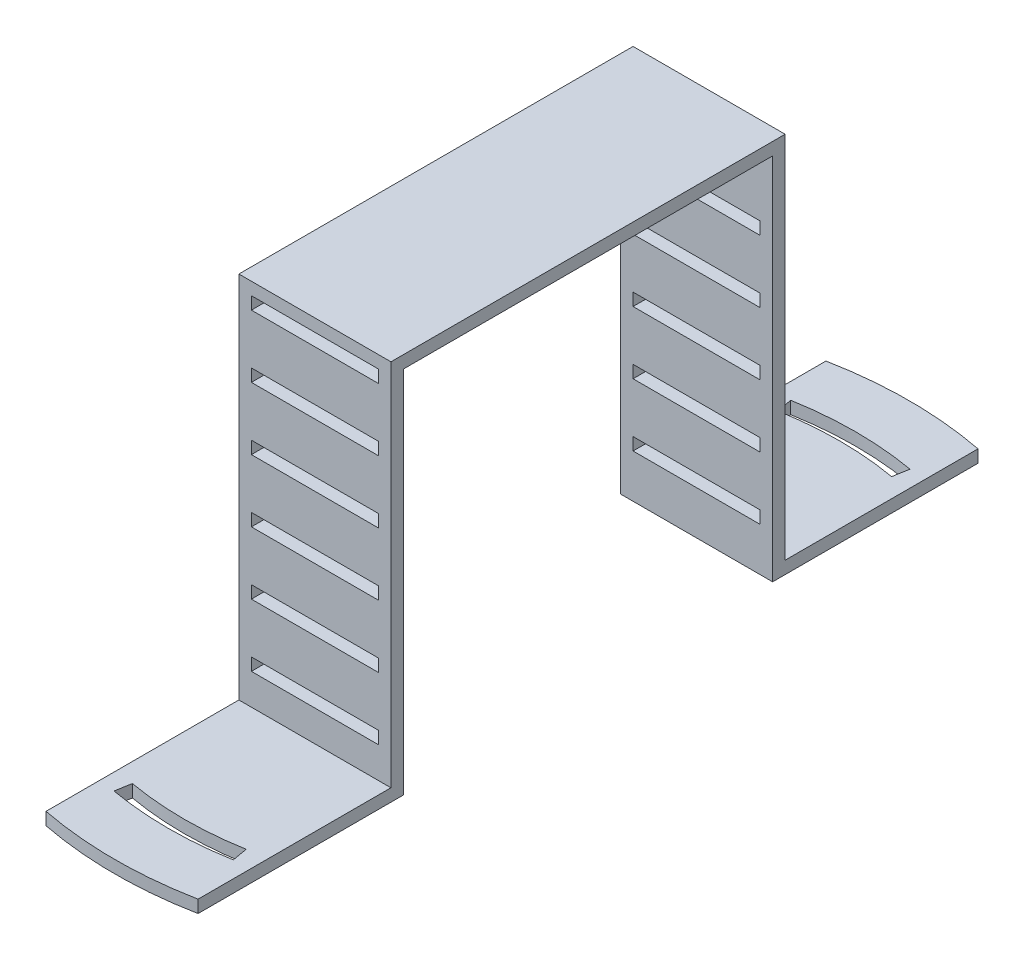
SolidWorks part; units mm, degrees
ref_plane "Front Plane" through (0, 0, 0) normal (0, 0, 1) x (1, 0, 0)
ref_plane "Top Plane" through (0, 0, 0) normal (0, 1, 0) x (1, 0, 0)
ref_plane "Right Plane" through (0, 0, 0) normal (1, 0, 0) x (0, 0, -1)
sketch "Sketch1" plane through (0, 0, 0) normal (0, 1, 0) x (1, 0, 0)
  line L0 (0, 0) -> (0, -79.375)
  line L1 (7.1438, -66.675) -> (-7.1437, -66.675)
  line L2 (50.8, 22.225) -> (76.2, 22.225)
  line L3 (-63.5, -47.625) -> (-50.8, -47.625)
  line L4 (-50.8, -47.625) -> (-50.8, 22.225)
  line L5 (63.5, -47.625) -> (50.8, -47.625)
  line L6 (50.8, -47.625) -> (50.8, 22.225)
  line L7 (-50.8, 22.225) -> (-76.2, 22.225)
  line L8 (0, 0) -> (-27.2811, 0)
  circle A0 centre (0, 0) radius 79.375
  circle A1 centre (-7.1437, -66.675) radius 1.5875
  circle A2 centre (7.1438, -66.675) radius 1.5875
  circle A3 centre (7.1438, 66.675) radius 1.5875
  circle A4 centre (-7.1437, 66.675) radius 1.5875
  point P7 (0, -66.675)
  dimension "D1" = 7.1437
  dimension "D3" = 50.8
  dimension "D6" = 3.175
  dimension "D2" = 12.7
  dimension "D4" = 69.85
  dimension "D5" = 47.625
extrude "Boss-Extrude5" add sketch "Sketch1" along normal blind 1.5875 contours A2 A0 L5 L6 L2 L7 L4 L3 A1 A3 region at (0, 0, -2.0947)
fillet "Fillet2" radius 2.54 1 edges at (-63.5, 0.7937, 47.625)
fillet "Fillet3" radius 2.54 1 edges at (63.5, 0.7937, 47.625)
fillet "Fillet4" radius 5.08 2 edges at (-76.2, 0.7937, -22.225) (76.2, 0.7937, -22.225)
sketch "Sketch2" plane through (0, 1.5875, 0) normal (0, 1, 0) x (1, 0, 0)
  line L0 (0, 0) -> (0, 79.375)
  line L1 (0, 0) -> (-67.0566, 0)
  line L2 (0, 0) -> (-61.0886, 27.6545)
  line L3 (0, 0) -> (-43.6778, 50.8806)
  line L4 (0, 0) -> (-63.2664, 22.225)
  line L5 (-50.8, 22.225) -> (-69.0955, 22.225) construction
  line L6 (0, 0) -> (0, 2.6153)
  line L7 (0, 0) -> (-39.0771, 54.4938)
  line L8 (0, 0) -> (-12.3858, 65.9028)
  line L9 (-62.5348, 28.3092) -> (-59.6424, 26.9998)
  line L10 (-43.6778, 50.8806) -> (-44.7118, 52.0852)
  line L11 (-43.6778, 50.8806) -> (-42.6438, 49.6761)
  line L12 (-39.0771, 54.4938) -> (-40.0022, 55.7839)
  line L13 (-39.0771, 54.4938) -> (-38.152, 53.2037)
  line L14 (-43.6778, 50.8806) -> (-42.6438, 49.6761)
  line L15 (-12.3858, 65.9028) -> (-12.0926, 64.3426)
  line L16 (-12.3858, 65.9028) -> (-12.679, 67.463)
  line L17 (61.5813, 22.225) -> (64.9466, 22.225)
  line L18 (50.8, 22.225) -> (69.0955, 22.225) construction
  line L19 (12.3858, 65.9028) -> (12.679, 67.463)
  line L20 (12.3858, 65.9028) -> (12.0926, 64.3426)
  line L21 (39.0771, 54.4938) -> (38.152, 53.2037)
  line L22 (43.6778, 50.8806) -> (42.6438, 49.6761)
  line L23 (39.0771, 54.4938) -> (40.0022, 55.7839)
  line L24 (43.6778, 50.8806) -> (42.6438, 49.6761)
  line L25 (43.6778, 50.8806) -> (44.7118, 52.0852)
  line L26 (62.5348, 28.3092) -> (59.6424, 26.9998)
  line L27 (-50.8, -41.2985) -> (-50.8, -43.7716)
  line L28 (-50.8, -47.625) -> (-50.8, 22.225) construction
  line L29 (50.8, -41.2985) -> (50.8, -46.1668)
  line L30 (50.8, -47.625) -> (50.8, 22.225) construction
  line L31 (39.0771, -54.4938) -> (40.0022, -55.7839)
  line L32 (39.0771, -54.4938) -> (38.152, -53.2037)
  line L33 (12.3858, -65.9028) -> (12.0926, -64.3426)
  line L34 (12.3858, -65.9028) -> (12.679, -67.463)
  line L35 (-12.3858, -65.9028) -> (-12.679, -67.463)
  line L36 (-12.3858, -65.9028) -> (-12.0926, -64.3426)
  line L37 (-39.0771, -54.4938) -> (-38.152, -53.2037)
  line L38 (-39.0771, -54.4938) -> (-40.0022, -55.7839)
  arc A0 (-63.2664, 22.225) -> (-50.8, -43.7716) centre (0, 0) ccw
  arc A1 (73.8199, 29.172) -> (-73.8199, 29.172) centre (0, 0) ccw construction
  circle A2 centre (-7.1437, 66.675) radius 2.3813
  circle A3 centre (7.1437, 66.675) radius 2.3813
  circle A4 centre (7.1437, -66.675) radius 2.3813
  circle A5 centre (-7.1437, -66.675) radius 2.3813
  arc A6 (12.679, -67.463) -> (40.0022, -55.7839) centre (0, 0) ccw
  arc A7 (-61.7686, 21.6988) -> (-50.8, -41.2985) centre (0, 0) ccw
  arc A8 (-44.7118, 52.0852) -> (-62.5348, 28.3092) centre (0, 0) ccw
  arc A9 (-42.6438, 49.6761) -> (-59.6424, 26.9998) centre (0, 0) ccw
  arc A10 (12.0926, 64.3426) -> (38.152, 53.2037) centre (0, 0) cw
  arc A11 (12.679, 67.463) -> (40.0022, 55.7839) centre (0, 0) cw
  arc A12 (42.6438, 49.6761) -> (59.6424, 26.9998) centre (0, 0) cw
  arc A13 (-12.679, 67.463) -> (-40.0022, 55.7839) centre (0, 0) ccw
  arc A14 (44.7118, 52.0852) -> (62.5348, 28.3092) centre (0, 0) cw
  arc A15 (-12.0926, 64.3426) -> (-38.152, 53.2037) centre (0, 0) ccw
  arc A16 (12.0926, -64.3426) -> (38.152, -53.2037) centre (0, 0) ccw
  arc A17 (-12.0926, -64.3426) -> (-38.152, -53.2037) centre (0, 0) cw
  arc A18 (50.8, -46.1668) -> (64.9466, 22.225) centre (0, 0) ccw
  arc A19 (50.8, -43.7716) -> (63.2664, 22.225) centre (0, 0) ccw
  arc A20 (50.8, -41.2985) -> (61.5813, 22.225) centre (0, 0) ccw
  arc A21 (-12.679, -67.463) -> (-40.0022, -55.7839) centre (0, 0) cw
  circle M13 centre (-7.1437, -66.675) radius 1.5875
  circle M14 centre (7.1438, -66.675) radius 1.5875
  circle M15 centre (7.1438, 66.675) radius 1.5875
  circle M16 centre (-7.1437, 66.675) radius 1.5875
  dimension "D2" = 4.7625
  dimension "D7" = 1.5875
  dimension "D8" = 3.175
  dimension "D1" = 5
  dimension "D3" = 25
  dimension "D4" = 5
  dimension "D5" = 25
extrude "Cut-Extrude1" cut sketch "Sketch2" against normal blind 2.54 contours A9 L3 L10 A8 L9 L2 | A15 L8 L16 A13 L12 L7 | A2 M16 | A3 M15 | A11 L19 L20 A10 L21 L23 | A14 L25 L22 A12 L26 | A21 L35 L36 A17 L37 L38 | A5 M13 | A4 M14 | A16 L33 L34 A6 L31 L32 region at (-53.2404, 1.5875, -39.9101) region at (-26.1525, 1.5875, -61.1833) region at (26.1525, 1.5875, -61.1833) region at (53.2404, 1.5875, -39.9101) region at (26.1525, 1.5875, 61.1833) region at (-26.1525, 1.5875, 61.1833) region at (-9.4576, 1.5875, -66.675) region at (4.8299, 1.5875, -66.675) region at (4.8299, 1.5875, 66.675) region at (-9.4576, 1.5875, 66.675)
sketch "Sketch3" plane through (0, 1.5875, 0) normal (0, 1, 0) x (1, 0, 0)
  line L0 (-50.8, 22.225) -> (-50.8, -47.625)
  line L1 (-50.8, -47.625) -> (-44.45, -47.625)
  line L2 (-50.8, 22.225) -> (-44.45, 22.225)
  line L3 (0, 0) -> (0, 32.9013)
  circle A0 centre (-44.45, -47.625) radius 1.5875
  circle A1 centre (-44.45, 22.225) radius 1.5875
  circle A2 centre (44.45, 22.225) radius 1.5875
  circle A3 centre (44.45, -47.625) radius 1.5875
  dimension "D2" = 3.175
  dimension "D4" = 3.175
  dimension "D1" = 6.35
  dimension "D3" = 6.35
extrude "Cut-Extrude2" cut sketch "Sketch3" against normal blind 2.54 contours A1 | A2 | A0 | A3 region at (-44.45, 1.5875, 46.0824) region at (-44.45, 1.5875, -23.7676) region at (44.45, 1.5875, -22.225) region at (44.45, 1.5875, 47.625)
sketch "Sketch4" plane through (0, 1.5875, 0) normal (0, 1, 0) x (1, 0, 0)
  line L0 (-44.45, -47.625) -> (-44.45, 22.225)
  line L1 (-44.45, 22.225) -> (-50.8, 22.225)
  line L2 (-50.8, -47.625) -> (-50.8, 22.225) construction
  line L3 (0, 0) -> (0, -67.5878)
  line L4 (44.45, -47.625) -> (44.45, 22.225)
  circle A0 centre (-44.45, 22.225) radius 1.5875
  circle A1 centre (-44.45, -12.7) radius 1.5875
  circle A2 centre (44.45, -12.7) radius 1.5875
  dimension "D2" = 3.175
  dimension "D1" = 69.85
extrude "Cut-Extrude3" cut sketch "Sketch4" against normal blind 2.54 contours L0 A1 | L0 A1 | A2 L4 | A2 L4 region at (-45.1238, 1.5875, 12.7) region at (-43.7762, 1.5875, 12.7) region at (43.7762, 1.5875, 12.7) region at (45.1238, 1.5875, 12.7)
sketch "Sketch5" plane through (0, 1.5875, 0) normal (0, 1, 0) x (1, 0, 0)
  line L0 (-50.8, -12.7) -> (-34.8, -12.7)
  line L1 (-50.8, -47.625) -> (-50.8, 22.225) construction
  line L2 (-50.8, 22.225) -> (-34.8, 22.225)
  line L3 (-34.8, 22.225) -> (-34.8, -12.7)
  line L4 (0, 0) -> (0, 64.5379)
  line L5 (-34.8, 22.225) -> (-19.8, 22.225)
  line L6 (-19.8, 22.225) -> (-19.8, -12.7)
  line L7 (-19.8, -12.7) -> (-34.8, -12.7)
  line L8 (19.8, -12.7) -> (34.8, -12.7)
  line L9 (19.8, 22.225) -> (19.8, -12.7)
  line L10 (34.8, 22.225) -> (19.8, 22.225)
  line L11 (34.8, 22.225) -> (34.8, -12.7)
  dimension "D1" = 16
  dimension "D2" = 16
extrude "Cut-Extrude4" cut sketch "Sketch5" against normal through all contours L7 L6 L5 L3 | L11 L10 L9 L8 region at (-27.3, 1.5875, -4.7625) region at (27.3, 1.5875, -4.7625)
fillet "Fillet5" radius 7.62 4 edges at (-19.8, 0.7937, 12.7) (-34.8, 0.7937, 12.7) (-19.8, 0.7937, -22.225) (-34.8, 0.7937, -22.225)
fillet "Fillet6" radius 7.62 4 edges at (34.8, 0.7937, 12.7) (34.8, 0.7937, -22.225) (19.8, 0.7937, -22.225) (19.8, 0.7937, 12.7)
sketch "Sketch6" plane through (0, 1.5875, 0) normal (0, 1, 0) x (1, 0, 0)
  line L0 (-50.8, 22.225) -> (-69.0955, 22.225)
  line L1 (-69.0955, 22.225) -> (-69.0955, 39.0667)
  line L2 (-50.8, 22.225) -> (-50.8, -60.9898)
  line L3 (50.8, 22.225) -> (69.0955, 22.225)
  line L4 (69.0955, 22.225) -> (69.0955, 39.0667)
  line L5 (50.8, 22.225) -> (50.8, -60.9898)
  circle A0 centre (0, 0) radius 79.375
extrude "Boss-Extrude6" add sketch "Sketch6" against normal blind 1.5875 contours L1 A0 L2 L0 | L5 A0 L4 L3 region at (-63.4454, 1.5875, 10.5781) region at (63.4454, 1.5875, 10.5781)
sketch "Sketch7" plane through (0, 0, 0) normal (0, -1, 0) x (1, 0, 0)
  circle A0 centre (0, 0) radius 79.375
extrude "Cut-Extrude5" cut sketch "Sketch7" against normal blind 0.5875
sketch "Sketch8" plane through (0, 1.5875, 0) normal (0, 1, 0) x (1, 0, 0)
  circle A0 centre (-44.45, -12.7) radius 1.5875
  circle A1 centre (44.45, -12.7) radius 1.5875
  circle A2 centre (-7.1437, -66.675) radius 2.3813
  circle A3 centre (7.1437, -66.675) radius 2.3812
  circle A4 centre (-7.1437, 66.675) radius 2.3812
  circle A5 centre (7.1437, 66.675) radius 2.3813
extrude "Boss-Extrude7" add sketch "Sketch8" against normal up to surface (1 mm away) up to face at (-53.0191, 0.5875, -39.7442)
sketch "Sketch9" plane through (0, 1.5875, 0) normal (0, 1, 0) x (1, 0, 0)
  line L0 (-44.45, 22.225) -> (-44.45, -1.0583)
  line L1 (-44.45, -1.0583) -> (-44.45, -24.3417)
  line L2 (0, 0) -> (0, 22.225)
  circle A0 centre (-44.45, -1.0583) radius 1.5875
  circle A1 centre (-44.45, -24.3417) radius 1.5875
  circle A2 centre (44.45, -24.3417) radius 1.5875
  circle A3 centre (44.45, -1.0583) radius 1.5875
  dimension "D2" = 23.2833
  dimension "D3" = 3.175
  dimension "D4" = 3.175
  dimension "D1" = 23.2833
extrude "Cut-Extrude7" cut sketch "Sketch9" against normal blind 2.54 contours A1 | L0 A0 L1 | L1 A0 L0 | A2 | A3 region at (-43.7762, 1.5875, 1.0583) region at (-43.3592, 1.5875, 23.2509) region at (-45.1238, 1.5875, 1.0583) region at (44.45, 1.5875, 24.3417) region at (44.45, 1.5875, 1.0583)
sketch "Sketch10" plane through (0, 1.5875, 0) normal (0, 1, 0) x (1, 0, 0)
  line L0 (-65.4691, 0) -> (-68.6441, 0)
  line L1 (65.4691, 0) -> (68.6441, 0)
  circle A0 centre (0, 0) radius 68.6441
  circle A1 centre (0, 0) radius 65.4691
  line M21 (12.0926, 64.3426) -> (12.679, 67.463)
  arc M22 (12.679, 67.463) -> (40.0022, 55.7839) centre (0, 0) cw
  line M23 (40.0022, 55.7839) -> (38.152, 53.2037)
  arc M24 (38.152, 53.2037) -> (12.0926, 64.3426) centre (0, 0) ccw
  line M25 (-12.679, 67.463) -> (-12.0926, 64.3426)
  arc M26 (-12.0926, 64.3426) -> (-38.152, 53.2037) centre (0, 0) ccw
  line M27 (-38.152, 53.2037) -> (-40.0022, 55.7839)
  arc M28 (-40.0022, 55.7839) -> (-12.679, 67.463) centre (0, 0) cw
  line M29 (-44.7118, 52.0852) -> (-42.6438, 49.6761)
  arc M30 (-42.6438, 49.6761) -> (-59.6424, 26.9998) centre (0, 0) ccw
  line M31 (-59.6424, 26.9998) -> (-62.5348, 28.3092)
  arc M32 (-62.5348, 28.3092) -> (-44.7118, 52.0852) centre (0, 0) cw
  line M33 (42.6438, 49.6761) -> (44.7118, 52.0852)
  arc M34 (44.7118, 52.0852) -> (62.5348, 28.3092) centre (0, 0) cw
  line M35 (62.5348, 28.3092) -> (59.6424, 26.9998)
  arc M36 (59.6424, 26.9998) -> (42.6438, 49.6761) centre (0, 0) ccw
extrude "Boss-Extrude8" add sketch "Sketch10" against normal up to surface (1 mm away) contours M29 M32 M31 M30 | M25 M28 M27 M26 | M21 M24 M23 M22 | M33 M36 M35 M34 region at (-53.2404, 1.5875, -39.9101) region at (53.2404, 1.5875, -39.9101) region at (-26.1525, 1.5875, -61.1833) region at (26.1525, 1.5875, -61.1833) up to face at (44.45, 0.5875, 22.7542)
sketch "Sketch11" plane through (0, 1.5875, 0) normal (0, 1, 0) x (1, 0, 0)
  line L0 (0, 0) -> (-68.6441, 0)
  line L1 (0, 0) -> (-67.6013, 11.9199)
  line L2 (0, 0) -> (-67.6013, -11.9199)
  line L3 (0, 0) -> (-56.1266, 56.1266)
  line L4 (0, 0) -> (-11.9199, 67.6013)
  line L5 (0, 0) -> (11.9199, 67.6013)
  line L6 (0, 0) -> (56.1266, -56.1266)
  line L7 (0, 0) -> (56.1266, 56.1266)
  line L8 (0, 0) -> (67.6013, 11.9199)
  line L9 (0, 0) -> (67.6013, -11.9199)
  line L10 (0, 0) -> (11.9199, -67.6013)
  line L11 (0, 0) -> (-11.9199, -67.6013)
  line L12 (0, 0) -> (-39.3726, 56.23)
  line L13 (0, 0) -> (-56.23, 39.3726)
  line L14 (0, 0) -> (0, 37.7088)
  line L15 (0, 0) -> (39.3726, 56.23)
  line L16 (0, 0) -> (56.23, 39.3726)
  circle A0 centre (0, 0) radius 68.6441
  circle A1 centre (0, 0) radius 65.4691
  circle A3 centre (0, 0) radius 79.375
  dimension "D3" = 158.75
  dimension "D1" = 10
  dimension "D2" = 10
  dimension "D4" = 45
  dimension "D5" = 20
  dimension "D6" = 180
  dimension "D7" = 90
  dimension "D8" = 35
  dimension "D9" = 10
  dimension "D10" = 10
extrude "Cut-Extrude9" cut sketch "Sketch11" against normal blind 2.54 contours A1 L11 A0 L10 | A1 L5 A0 L4 | A1 L12 A0 L3 | A1 L3 A0 L13 | A1 L1 A0 L0 | A1 L0 A0 L2 | A1 L9 A0 L8 | A1 L16 A0 L7 | A1 L7 A0 L15 region at (-66.7291, 1.5875, 5.838) region at (-66.7291, 1.5875, -5.838) region at (-51.3128, 1.5875, -43.0565) region at (-43.0565, 1.5875, -51.3128) region at (0, 1.5875, -66.7291) region at (43.0565, 1.5875, -51.3128) region at (51.3128, 1.5875, -43.0565) region at (66.7291, 1.5875, 0) region at (0, 1.5875, 66.7291)
sketch "Sketch12" plane through (0, 1.5875, 0) normal (0, 1, 0) x (1, 0, 0)
  line L0 (0, 0) -> (-40.0022, -55.7839)
  line L1 (0, 0) -> (-18.5106, -66.1012)
  line L2 (0, 0) -> (0, -68.6441)
  line L3 (0, 0) -> (18.5106, -66.1012)
  line L4 (0, 0) -> (40.0022, -55.7839)
  line L5 (-12.0926, -64.3426) -> (-12.679, -67.463)
  line L6 (12.0926, -64.3426) -> (12.679, -67.463)
  circle A0 centre (0, 0) radius 68.6441
  circle A1 centre (0, 0) radius 65.4691
  dimension "D1" = 20
extrude "Boss-Extrude9" add sketch "Sketch12" against normal up to surface (1 mm away) contours A1 L1 A0 L5 | A1 L6 A0 L3 region at (-15.2467, 1.5875, 65.2913) region at (15.2467, 1.5875, 65.2913) up to face at (66.5472, 0.5875, 0)
sketch "Sketch13" plane through (0, 1.5875, 0) normal (0, 1, 0) x (1, 0, 0)
  line L0 (0, 0) -> (-67.6013, 11.9199)
  line L1 (0, 0) -> (-11.9199, 67.6013)
  line L2 (0, 0) -> (-64.5044, 23.4777)
  line L3 (0, 0) -> (-52.5844, 44.1236)
  line L4 (0, 0) -> (-44.1236, 52.5844)
  line L5 (0, 0) -> (-23.4777, 64.5044)
  line L6 (0, 0) -> (0, 68.6441)
  line L7 (0, 0) -> (23.4777, 64.5044)
  line L8 (0, 0) -> (44.1236, 52.5844)
  line L9 (0, 0) -> (52.5844, 44.1236)
  line L10 (0, 0) -> (64.5044, 23.4777)
  line L11 (0, 0) -> (-68.6441, 0)
  line L12 (0, 0) -> (64.5044, -23.4777)
  line L13 (0, 0) -> (52.5844, -44.1236)
  line L14 (0, 0) -> (-52.5844, -44.1236)
  line L15 (0, 0) -> (-64.5044, -23.4777)
  circle A1 centre (0, 0) radius 68.6441
  circle A2 centre (0, 0) radius 65.4691
  dimension "D1" = 70
  dimension "D2" = 10
  dimension "D3" = 20
  dimension "D4" = 10
  dimension "D5" = 20
  dimension "D6" = 10
  dimension "D7" = 90
extrude "Cut-Extrude10" cut sketch "Sketch13" against normal blind 2.54 contours A2 L15 A1 L14 | A2 L13 A1 L12 | A2 L10 A1 L9 | A2 L8 A1 L7 | A2 L5 A1 L4 | A2 L3 A1 L2 region at (-57.7891, 1.5875, -33.3646) region at (-33.3646, 1.5875, -57.7891) region at (33.3646, 1.5875, -57.7891) region at (57.7891, 1.5875, -33.3646) region at (57.7891, 1.5875, 33.3646) region at (-57.7891, 1.5875, 33.3646)
sketch "Sketch15" plane through (0, 1.5875, 0) normal (0, 1, 0) x (1, 0, 0)
  line L0 (0, 0) -> (-64.5044, 23.4777)
  line L1 (0, 0) -> (-52.5844, 44.1236)
  line L2 (0, 0) -> (-44.1236, 52.5844)
  line L3 (0, 0) -> (0, 68.6441)
  line L4 (0, 0) -> (44.1236, 52.5844)
  line L5 (0, 0) -> (52.5844, 44.1236)
  circle A0 centre (0, 0) radius 68.6441
  circle A1 centre (0, 0) radius 65.4691
  dimension "D1" = 20
  dimension "D2" = 10
extrude "Boss-Extrude10" add sketch "Sketch15" against normal up to surface (1 mm away) contours A1 L2 A0 L1 | A1 L5 A0 L4 region at (-47.3649, 1.5875, -47.3649) region at (47.3649, 1.5875, -47.3649) up to face at (-57.6316, 0.5875, 33.2736)
sketch "Sketch16" plane through (0, 1.5875, 0) normal (0, 1, 0) x (1, 0, 0)
  line L0 (0, 0) -> (-11.9199, -67.6013)
  line L1 (0, 0) -> (-23.4777, -64.5044)
  line L2 (0, 0) -> (-44.1236, -52.5844)
  line L3 (0, 0) -> (0, -68.6441)
  line L4 (0, 0) -> (23.4777, -64.5044)
  line L5 (0, 0) -> (44.1236, -52.5844)
  circle A0 centre (0, 0) radius 68.6441
  circle A1 centre (0, 0) radius 65.4691
  dimension "D1" = 10
  dimension "D2" = 20
extrude "Cut-Extrude11" cut sketch "Sketch16" against normal blind 2.54 contours A1 L2 A0 L1 | A1 L4 A0 L5 region at (-33.3646, 1.5875, 57.7891) region at (33.3646, 1.5875, 57.7891)
sketch "Sketch17" plane through (0, 1.5875, 0) normal (0, 1, 0) x (1, 0, 0)
  line L0 (0, 0) -> (0, -68.6441)
  line L1 (0, 0) -> (-11.9199, -67.6013)
  line L2 (0, 0) -> (-23.4777, -64.5044)
  line L3 (0, 0) -> (11.9199, -67.6013)
  line L4 (0, 0) -> (23.4777, -64.5044)
  arc A0 (-11.9199, -67.6013) -> (11.9199, -67.6013) centre (0, 0) ccw construction
  circle A1 centre (0, 0) radius 68.6441
  circle A2 centre (0, 0) radius 65.4691
  dimension "D1" = 10
extrude "Boss-Extrude11" add sketch "Sketch17" against normal up to surface (1 mm away) contours A2 L2 A1 L1 | A2 L3 A1 L4 region at (-17.3367, 1.5875, 64.7016) region at (17.3367, 1.5875, 64.7016) up to face at (-30.945, 0.5875, 58.6377)
sketch "Sketch18" plane through (0, 1.5875, 0) normal (0, 1, 0) x (1, 0, 0)
  line L0 (0, -20) -> (-12.8901, -20)
  line L1 (-79.375, 0) -> (79.375, 0)
  line L2 (11.3686, -64.4745) -> (11.9199, -67.6013)
  line L3 (0, 39.375) -> (0, -79.375)
  line L4 (-11.9199, -67.6013) -> (-11.3686, -64.4745)
  line L5 (11.3686, 64.4745) -> (11.9199, 67.6013)
  line L6 (-11.9199, 67.6013) -> (-11.3686, 64.4745)
  line L11 (-15.1902, 77.9079) -> (-15.1902, 39.375)
  line L12 (-15.1902, 39.375) -> (15.1902, 39.375)
  line L13 (15.1902, 77.9079) -> (15.1902, 39.375)
  line L14 (15.1902, -77.9079) -> (15.1902, -39.375)
  line L15 (-15.1902, -39.375) -> (15.1902, -39.375)
  line L16 (-15.1902, -77.9079) -> (-15.1902, -39.375)
  line L19 (-11.9199, -67.6013) -> (-11.3686, -64.4745)
  line L20 (11.3686, -64.4745) -> (11.9199, -67.6013)
  circle A0 centre (0, 0) radius 79.375 construction
  arc A1 (11.3686, 64.4745) -> (-11.3686, 64.4745) centre (0, 0) ccw
  arc A2 (11.9199, 67.6013) -> (-11.9199, 67.6013) centre (0, 0) ccw
  arc A3 (11.9199, -67.6013) -> (-11.9199, -67.6013) centre (0, 0) cw
  arc A4 (11.9199, -67.6013) -> (-11.9199, -67.6013) centre (0, 0) cw
  arc A5 (11.3686, -64.4745) -> (-11.3686, -64.4745) centre (0, 0) cw
  arc A6 (11.3686, -64.4745) -> (-11.3686, -64.4745) centre (0, 0) cw
  circle A7 centre (0, 0) radius 79.375
extrude "Boss-Extrude13" add sketch "Sketch18" along normal blind 2.5 contours L13 A7 L11 L12 A2 L5 A1 L6 | L16 A7 L3 A3 L4 A5 L15 | L3 A7 L14 L15 A5 L2 A3 region at (0, 1.5875, -58.6326) region at (-7.6611, 1.5875, 58.6326) region at (7.6611, 1.5875, 58.6326)
sketch "Sketch19" plane through (15.1902, 0, 0) normal (1, 0, 0) x (0, 0, -1)
  line L0 (0, 1.5875) -> (0, 17.5736)
  line L1 (-39.375, 1.5875) -> (-36.875, 1.5875)
  line L2 (-39.375, 1.5875) -> (-39.375, 77.7875)
  line L3 (-39.375, 77.7875) -> (-36.875, 77.7875)
  line L4 (-36.875, 1.5875) -> (-36.875, 77.7875)
  line L5 (77.9079, 1.5875) -> (-77.9079, 1.5875) construction
  line L6 (36.875, 1.5875) -> (36.875, 77.7875)
  line L7 (39.375, 77.7875) -> (36.875, 77.7875)
  line L8 (39.375, 1.5875) -> (39.375, 77.7875)
  line L9 (39.375, 1.5875) -> (36.875, 1.5875)
  line L10 (-36.875, 77.7875) -> (36.875, 77.7875)
  line L11 (-36.875, 75.2875) -> (36.875, 75.2875)
  line M2 (-39.375, 1.5875) -> (-39.375, 4.0875)
  dimension "D1" = 2.5
  dimension "D2" = 76.2
  dimension "D3" = 2.5
extrude "Boss-Extrude14" add sketch "Sketch19" against normal up to surface (30.3805 mm away) contours L1 L4 L3 L2 M2 | L4 L11 L6 L10 | L9 L8 L7 L6 region at (15.1902, 39.6875, 38.125) region at (15.1902, 76.5375, 0) region at (15.1902, 39.6875, -38.125) up to face at (-15.1902, 2.8375, 58.6415)
sketch "Sketch20" plane through (0, 1.5875, 0) normal (0, 1, 0) x (1, 0, 0)
  circle A0 centre (0, 0) radius 79.375
extrude "Cut-Extrude12" cut sketch "Sketch20" against normal blind 2.5
sketch "Sketch21" plane through (0, 0, -39.375) normal (0, 0, -1) x (-1, 0, 0)
  line L0 (-15.1902, 4.0875) -> (-15.1902, 77.7875) construction
  line L1 (15.1902, 77.7875) -> (-15.1902, 77.7875)
  line L2 (15.1902, 77.7875) -> (15.1902, 75.2875)
  line L3 (15.1902, 75.2875) -> (-15.1902, 75.2875)
  line L4 (-15.1902, 77.7875) -> (-15.1902, 75.2875)
  line L5 (15.1902, 4.0875) -> (15.1902, 77.7875) construction
  line L6 (-12.6902, 75.2875) -> (12.6902, 75.2875)
  line L7 (-12.6902, 75.2875) -> (-12.6902, 72.7875)
  line L8 (-12.6902, 72.7875) -> (12.6902, 72.7875)
  line L9 (12.6902, 75.2875) -> (12.6902, 72.7875)
  line L10 (-15.1902, 67.7875) -> (15.1902, 67.7875)
  line L11 (-15.1902, 4.0875) -> (-15.1902, 77.7875) construction
  line L12 (12.6902, 60.2875) -> (12.6902, 62.7875)
  line L13 (-12.6902, 62.7875) -> (12.6902, 62.7875)
  line L14 (-12.6902, 60.2875) -> (-12.6902, 62.7875)
  line L15 (-12.6902, 60.2875) -> (12.6902, 60.2875)
  line L16 (-15.1902, 55.2875) -> (15.1902, 55.2875)
  line L17 (-12.6902, 50.2875) -> (12.6902, 50.2875)
  line L18 (-12.6902, 50.2875) -> (-12.6902, 47.7875)
  line L19 (-12.6902, 47.7875) -> (12.6902, 47.7875)
  line L20 (12.6902, 50.2875) -> (12.6902, 47.7875)
  line L21 (12.6902, 35.2875) -> (12.6902, 37.7875)
  line L22 (-12.6902, 37.7875) -> (12.6902, 37.7875)
  line L23 (-12.6902, 35.2875) -> (-12.6902, 37.7875)
  line L24 (-12.6902, 35.2875) -> (12.6902, 35.2875)
  line L25 (-15.1902, 30.2875) -> (15.1902, 30.2875)
  line L26 (-12.6902, 25.2875) -> (12.6902, 25.2875)
  line L27 (-12.6902, 25.2875) -> (-12.6902, 22.7875)
  line L28 (-12.6902, 22.7875) -> (12.6902, 22.7875)
  line L29 (12.6902, 25.2875) -> (12.6902, 22.7875)
  line L30 (12.6902, 10.2875) -> (12.6902, 12.7875)
  line L31 (-12.6902, 12.7875) -> (12.6902, 12.7875)
  line L32 (-12.6902, 10.2875) -> (-12.6902, 12.7875)
  line L33 (-12.6902, 10.2875) -> (12.6902, 10.2875)
  dimension "D1" = 2.5
  dimension "D2" = 2.5
  dimension "D3" = 2.5
  dimension "D4" = 2.5
  dimension "D5" = 5
  dimension "D6" = 5
  dimension "D7" = 5
extrude "Cut-Extrude15" cut sketch "Sketch21" against normal through all contours L14 L15 L12 L13 | L20 L17 L18 L19 | L29 L26 L27 L28 | L32 L33 L30 L31 | L9 L3 L7 L8 | L23 L24 L21 L22 region at (0, 74.0375, -39.375) region at (0, 61.5375, -39.375) region at (0, 49.0375, -39.375) region at (0, 36.5375, -39.375) region at (0, 24.0375, -39.375) region at (0, 11.5375, -39.375)
